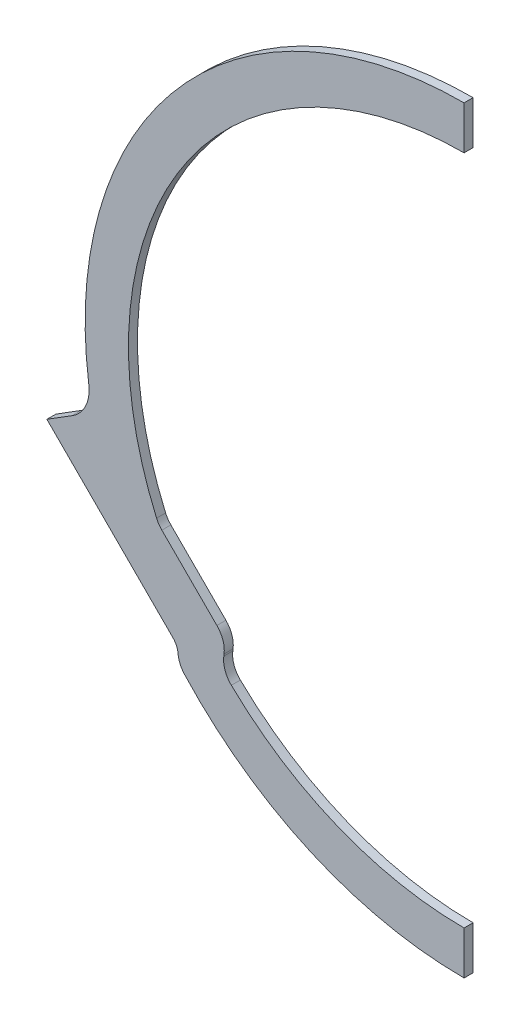
SolidWorks part; units mm, degrees
material "Balsa"
ref_plane "Front Plane" through (0, 0, 0) normal (0, 0, 1) x (1, 0, 0)
ref_plane "Top Plane" through (0, 0, 0) normal (0, 1, 0) x (1, 0, 0)
ref_plane "Right Plane" through (0, 0, 0) normal (1, 0, 0) x (0, 0, -1)
sketch "Sketch1" plane through (0, 0, 0) normal (0, 0, 1) x (1, 0, 0)
  line L0 (0, -110.0909) -> (0, -70.6286) construction
  line L1 (0, 0) -> (0, 245.1538) construction
  line L2 (0, 0) -> (0, 631.6453) construction
  line L3 (-120.188, -34.2725) -> (-99.9824, -54.478)
  line L4 (0, 0) -> (-284.8905, 0) construction
  line L5 (-99.9824, -54.478) -> (-101.1426, -63.4095)
  line L8 (-99.9824, -54.478) -> (-57.7675, -96.693) construction
  line L9 (-99.9824, -54.478) -> (0, 0) construction
  line L10 (-101.1426, -63.4095) -> (0, 0) construction
  arc A0 (-57.7675, -96.693) -> (-120.188, -34.2725) centre (0, 23.495) ccw
  arc A2 (-120.188, -34.2725) -> (-57.7675, -96.693) centre (0, 23.495) ccw construction
  arc A3 (-101.1426, -63.4095) -> (-57.7675, -96.693) centre (0, 23.495) ccw
  point P2 (0, 156.7839)
  point P3 (0, -109.8059)
  point P15 (-99.9824, -54.478)
  dimension "D1" = 266.5898
  dimension "D2" = 266.7
  dimension "D3" = 23.495
  dimension "D5" = 109.22
  dimension "D6" = 45
  dimension "D7" = 28.575
  dimension "D4" = 3.5
extrude "Boss-Extrude1" add sketch "Sketch1" along normal mid plane 3.175
sketch "Sketch2" plane through (0, 0, 1.5875) normal (0, 0, 1) x (1, 0, 0)
  line L4 (-83.9033, -49.0045) -> (-85.1218, -58.3845)
  line L5 (-107.5191, -25.3887) -> (-83.9033, -49.0045)
  line L6 (-83.9033, -49.0045) -> (-85.1218, -58.3845)
  line L7 (-107.5191, -25.3887) -> (-83.9033, -49.0045)
  arc A2 (-85.1218, -58.3845) -> (-107.5191, -25.3887) centre (0, 23.495) ccw
  arc A3 (-85.1218, -58.3845) -> (-107.5191, -25.3887) centre (0, 23.495) ccw
  dimension "D1" = 15.24
extrude "Cut-Extrude1" cut sketch "Sketch2" against normal up to surface (3.175 mm away) up to face at (-33.0092, -2.288, -1.5875)
fillet "Fillet1" radius 8.89 6 edges at (-107.5191, -25.3887, 0) (-120.188, -34.2725, 0) (-101.1426, -63.4095, 0) (-99.9824, -54.478, 0) (-83.9033, -49.0045, 0) (-85.1218, -58.3845, 0)
sketch "Sketch3" plane through (0, 0, 0) normal (1, 0, 0) x (0, 0, -1)
  line L1 (-107.0531, 227.715) -> (127.3903, 227.715)
  line L2 (-107.0531, 227.715) -> (-107.0531, -194.8481)
  line L3 (-107.0531, -194.8481) -> (127.3903, -194.8481)
  line L4 (127.3903, 227.715) -> (127.3903, -194.8481)
extrude "Cut-Extrude2" cut sketch "Sketch3" along normal through all
sketch "Sketch5" plane through (0, 0, 0) normal (0, 0, 1) x (1, 0, 0)
  line L0 (-146.8166, -13.0034) -> (-125.2935, 0.4458)
  line L1 (-146.8166, -13.0034) -> (-100.6004, -59.2359)
  line L2 (0, 0) -> (-240.0313, 0) construction
  line L3 (-100.6004, -59.2359) -> (-91.9691, -50.6076)
  line L4 (-91.9691, -50.6076) -> (-125.2935, 0.4458)
  ellipse E0 centre (0.6289, 30.2513) end of major axis (130.0331, 30.2513) minor radius 129.3587 (-127.7603, 14.0811) -> (-84.313, -67.3377) ccw construction
  dimension "D1" = 45.01
  dimension "D2" = 113.0265
  dimension "D3" = 116.7447
  dimension "D4" = 32
  dimension "D5" = 65.3711
extrude "Boss-Extrude2" add sketch "Sketch5" along normal mid plane 3.175
fillet "Fillet2" radius 6.35 1 edges at (-100.6004, -59.2359, 0)
fillet "Fillet3" radius 12.7 1 edges at (-130.7045, -2.9354, 0)
